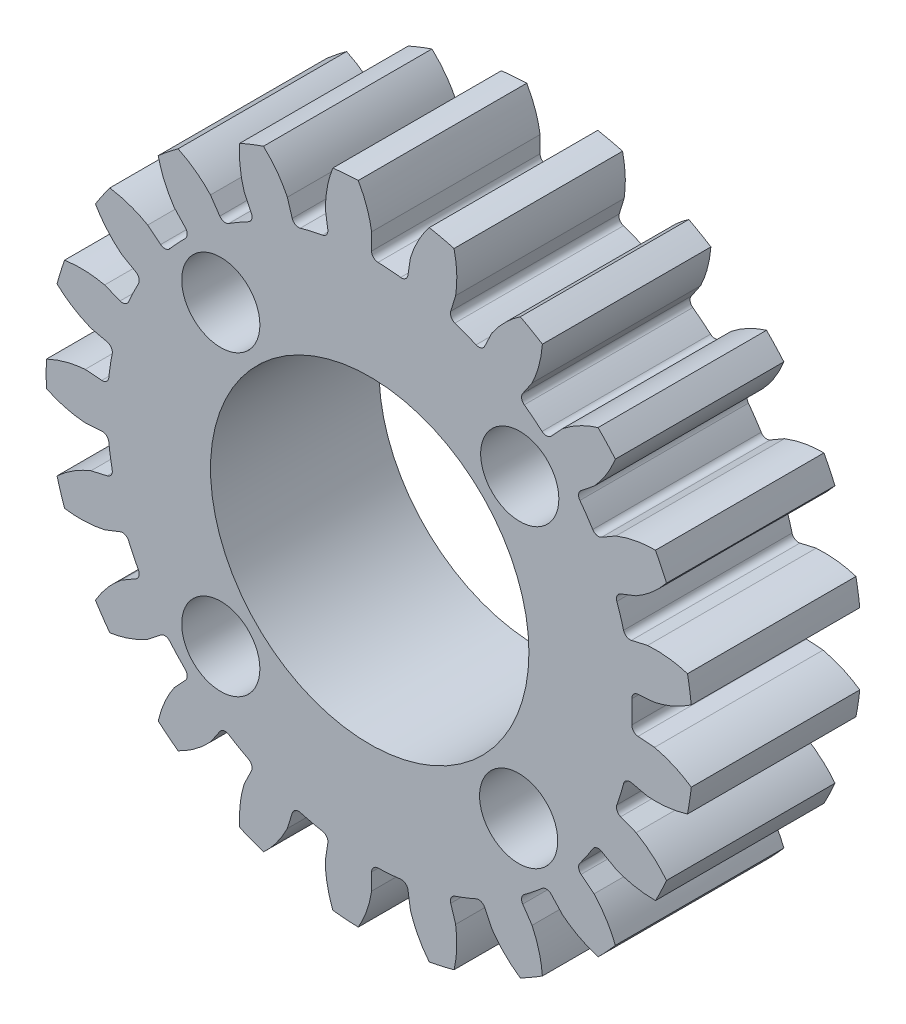
SolidWorks part; units mm, degrees
ref_plane "Front" through (0, 0, 0) normal (0, 0, 1) x (1, 0, 0)
ref_plane "Top" through (0, 0, 0) normal (0, 1, 0) x (1, 0, 0)
ref_plane "Right" through (0, 0, 0) normal (1, 0, 0) x (0, 0, -1)
sketch "Sketch1" plane through (0, 0, 0) normal (0, 0, 1) x (1, 0, 0)
  line L0 (-266.7, 0) -> (266.7, 0) construction
  circle A0 centre (0, 0) radius 12.192
  circle A1 centre (0, 0) radius 11.1125 construction
  circle A3 centre (0, 0) radius 9.888 construction
  dimension "D1" = 1.2245
  dimension "D2" = 2.304
  dimension "D3" = 1.0795
extrude "Boss-Extrude1" add sketch "Sketch1" against normal blind 6.35
sketch "Sketch2" plane through (0, 0, 0) normal (1, 0, 0) x (0, 0, -1)
  line L0 (6.35, 0) -> (14.2875, 0)
  line L1 (6.35, 0) -> (6.35, 9.525)
  line L2 (6.35, 9.525) -> (14.2875, 9.525)
  line L3 (14.2875, 9.525) -> (14.2875, 0)
  point P5 (14.2875, -9.525)
sketch "Sketch3" plane through (0, 0, 0) normal (0, 0, 1) x (1, 0, 0)
  line L0 (0, 0) -> (0, 12.192) construction
  line L1 (-2.6937, 10.4159) -> (0, 11.1125)
  line L2 (-9.5921, 11.1125) -> (9.5921, 11.1125) construction
  line L3 (-9.2865, 8.7108) -> (9.2865, 13.5142) construction
  line L4 (-2.6937, 10.4159) -> (0, 0) construction
  line L5 (-6.6544, 8.4537) -> (0, 0) construction
  line L6 (-6.6544, 8.4537) -> (-0.9701, 12.9282) construction
  line L7 (-1.8783, 10.5933) -> (0, 0) construction
  line L8 (-1.8783, 10.5933) -> (0.0394, 10.9333) construction
  arc A0 (-2.6937, 10.4159) -> (-6.6544, 8.4537) centre (0, 0) ccw
  circle A1 centre (0, 0) radius 11.1125 construction
  circle A2 centre (0, 0) radius 10.7585 construction
  arc A3 (-2.6937, 10.4159) -> (-1.8783, 10.5933) centre (0, 0) cw
  circle A4 centre (0, 0) radius 12.192 construction
  point P6 (0, 11.1125)
  dimension "D1" = 2.7823
  dimension "D3" = 7.2341
  dimension "D5" = 1.9476
  dimension "D2" = 4.4518
  dimension "D4" = 0.8347
sketch "Sketch4" plane through (0, 0, 0) normal (0, 0, 1) x (1, 0, 0)
  line L0 (0, 0) -> (0.8281, 11.0504) construction
  line L1 (0.0699, 10.7583) -> (0.0699, 9.8878)
  line L2 (0, 11.1125) -> (1.6562, 10.9884) construction
  line L3 (1.5343, 10.6486) -> (1.4046, 9.7877)
  line L4 (0.0699, 9.8878) -> (0, 0) construction
  line L5 (0, 0) -> (0, 12.192) construction
  arc A0 (1.4046, 9.7877) -> (0.0699, 9.8878) centre (0, 0) ccw
  arc A1 (0, 11.1125) -> (1.6562, 10.9884) centre (0, 0) cw construction
  circle A2 centre (0, 0) radius 11.1125 construction
  circle A3 centre (0, 0) radius 10.7585 construction
  circle A4 centre (0, 0) radius 9.888 construction
  arc A5 (2.8861, 12.6392) -> (-0.9701, 12.9282) centre (0, 0) ccw
  spline S0 degree 2 poles (-0.9701, 12.9282) (-0.1124, 11.9553) (0.0699, 10.7583) knots 0 0 0 1 1 1
  spline S1 degree 2 poles (2.8861, 12.6392) (1.893, 11.8051) (1.5343, 10.6486) knots 0 0 0 1 1 1
  dimension "D1" = 1.6624
extrude "Cut-Extrude1" cut sketch "Sketch4" against normal through all
fillet "Fillet1" radius 0.2494 2 edges at (1.4046, 9.7877, -3.175) (0.0699, 9.8878, -3.175)
pattern_circular "CirPattern1" count 21 over 360 about axis through (0, 0, -6.35) along (0, 0, 1) of "Cut-Extrude1", "Fillet1"
sketch "Sketch5" plane through (0, 0, 0) normal (0, 0, 1) x (1, 0, 0)
  circle A0 centre (0, 0) radius 6
  circle A1 centre (0, 0) radius 4.7625 construction
  dimension "Bore Min" = 12
  dimension "Bore Max" = 9.525
extrude "Cut-Extrude2" cut sketch "Sketch5" against normal through all
sketch "Pitch Dia" plane through (0, 0, 0) normal (0, 0, 1) x (1, 0, 0)
  circle A0 centre (0, 0) radius 11.1125 construction
  circle A1 centre (0, 0) radius 11.1125
sketch "Sketch6" plane through (0, 0, 0) normal (0, 0, 1) x (1, 0, 0)
  circle A0 centre (0, 0) radius 7.9375
  dimension "D1" = 15.875
hole_wizard "#4 Clearance Hole1" positions "Sketch7" profile "Sketch8" hole size "#4" standard "ANSI Inch"
sketch "Sketch7" plane through (0, 0, 0) normal (0, 0, 1) x (1, 0, 0)
  line L1 (-5.6127, 5.6127) -> (5.6127, 5.6127)
  line L2 (-5.6127, 5.6127) -> (-5.6127, -5.6127)
  line L3 (-5.6127, -5.6127) -> (5.6127, -5.6127)
  line L4 (5.6127, 5.6127) -> (5.6127, -5.6127)
  circle A0 centre (0, 0) radius 7.9375 construction
  point P0 (-5.6127, 5.6127)
  point P4 (5.6542, 5.5708)
  point P6 (5.6127, -5.6127)
  point P8 (-5.6127, -5.6127)
  point P59 (0, 0)
  point P60 (0, 0)
  point P61 (0, 0)
sketch "Sketch8" plane through (-5.6127, 5.6127, 0) normal (1, 0, 0) x (0, -1, 0)
  line L0 (0, 0) -> (0, 52.4472)
  line L1 (0, 52.4472) -> (1.4732, 51.562)
  line L2 (1.4732, 51.562) -> (1.4732, 0)
  line L5 (1.4732, 0) -> (0, 0)
  line L10 (0, 52.4472) -> (-1.4732, 51.562) construction
  line L11 (0, -6.35) -> (0, 107.95) construction
  dimension "Hole Dia." = 2.9464
  dimension "Hole Depth" = 51.562
  dimension "Drill Angle" = 118
equation "\"D1@Boss-Extrude1\" = \"Face Wd@Sketch2\""
equation "\"D2@Sketch3\" = \"D1@Sketch3\"*1.6"
equation "\"D3@Sketch3\" = \"D1@Sketch3\"+\"D2@Sketch3\""
equation "\"D4@Sketch3\" = \"D1@Sketch3\"*.3"
equation "\"D5@Sketch3\" = \"D1@Sketch3\"-\"D4@Sketch3\""
equation "\"D1@Sketch4\" = 1.5708/(\"Number of Teeth@Sketch1\"/\"Ptich Dia@Sketch1\")"
equation "\"D1@Chamfer1\" = \"B Hub Dia@Sketch2\"*.025"
equation "\"D1@CirPattern1\" = \"Number of Teeth@Sketch1\""
equation "\"D1@Fillet1\" = \"D1@Sketch4\"*.15"
equation "\"D1@Fillet2\" = \"OD@Sketch1\"*.01"
equation "\"D1@Sketch1\" = 1.157/(\"Number of Teeth@Sketch1\"/\"Ptich Dia@Sketch1\")"
